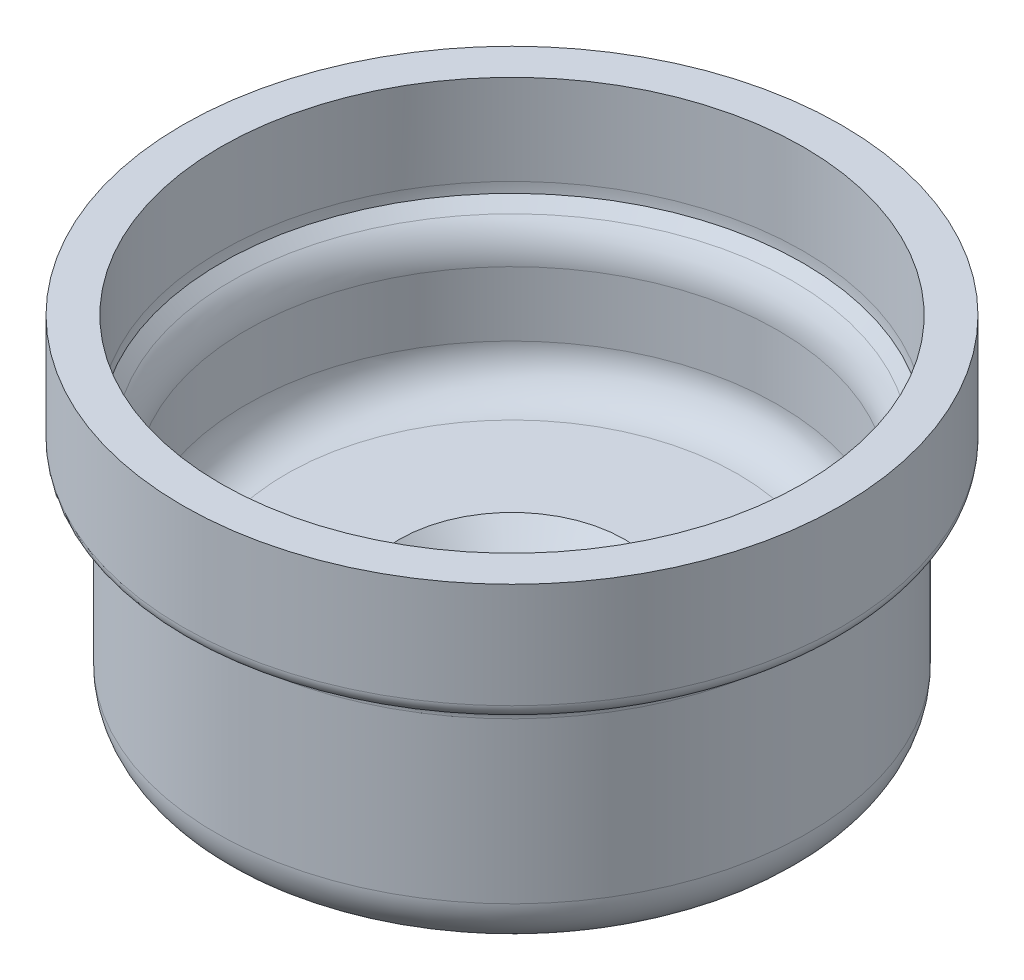
SolidWorks part; units mm, degrees
ref_plane "Front Plane" through (0, 0, 0) normal (0, 0, 1) x (1, 0, 0)
ref_plane "Top Plane" through (0, 0, 0) normal (0, 1, 0) x (1, 0, 0)
ref_plane "Right Plane" through (0, 0, 0) normal (1, 0, 0) x (0, 0, -1)
sketch "Sketch1" plane through (0, 0, 0) normal (0, 1, 0) x (1, 0, 0)
  circle A0 centre (0, 0) radius 26.55
  circle A1 centre (0, 0) radius 29.55
  dimension "D1" = 53.1
  dimension "D2" = 3
extrude "Boss-Extrude1" add sketch "Sketch1" along normal blind 15
sketch "Sketch2" plane through (0, 0, 0) normal (0, -1, 0) x (1, 0, 0)
  circle A0 centre (0, 0) radius 29.55 construction
  circle A1 centre (0, 0) radius 29.55
extrude "Boss-Extrude2" add sketch "Sketch2" along normal blind 10
chamfer "Chamfer1" distance 2.5 angle 45 1 edges at (0, 15, 26.55)
fillet "Fillet1" radius 4 1 edges at (0, 0, 26.55)
sketch "Sketch4" plane through (0, 15, 0) normal (0, 1, 0) x (1, 0, 0)
  circle A0 centre (0, 0) radius 32.9
  circle A1 centre (0, 0) radius 29.1
  dimension "D1" = 65.8
  dimension "D2" = 58.2
extrude "Boss-Extrude3" add sketch "Sketch4" along normal blind 10
sketch "Sketch5" plane through (0, 15, 0) normal (0, -1, 0) x (1, 0, 0)
  circle A0 centre (0, 0) radius 29.55 construction
  circle A1 centre (0, 0) radius 32.9
  circle A2 centre (0, 0) radius 32.9
  circle A3 centre (0, 0) radius 29.55
  dimension "D1" = 0
extrude "Boss-Extrude4" add sketch "Sketch5" along normal blind 2
fillet "Fillet3" radius 2 1 edges at (0, 13, -29.55)
fillet "Fillet6" radius 5 1 edges at (0, 12.5, 26.55)
fillet "Fillet7" radius 5 1 edges at (0, -10, -29.55)
fillet "Fillet8" radius 1.5 1 edges at (0, 13, -32.9)
sketch "Sketch6" plane through (0, 0, 0) normal (0, 1, 0) x (1, 0, 0)
  circle A0 centre (0, 0) radius 8.25
  dimension "D1" = 16.5
extrude "Cut-Extrude1" cut sketch "Sketch6" against normal blind 7
chamfer "Chamfer4" distance 3 angle 45 1 edges at (0, 0, 8.25)
sketch "Sketch7" plane through (0, -7, 0) normal (0, 1, 0) x (1, 0, 0)
  circle A0 centre (0, 0) radius 4.1
  dimension "D1" = 8.2
extrude "Cut-Extrude2" cut sketch "Sketch7" against normal through all
sketch "Sketch8" plane through (0, 0, 0) normal (0, 0, 1) x (1, 0, 0)
  line L0 (0, -10) -> (0, 27.7771) construction
  line L1 (-4.1, -10) -> (4.1, -10) construction
  line L2 (-24.55, -10) -> (24.55, -10) construction
  line L3 (22.55, -10) -> (12.55, -10)
  arc A0 (12.55, -10) -> (22.55, -10) centre (17.55, -10) cw
  dimension "D1" = 5
  dimension "D2" = 7
  dimension "D3" = 10
revolve "Cut-Revolve1" cut sketch "Sketch8" angle 360 about L0
fillet "Fillet9" radius 2 1 edges at (0, -10, -22.55)
fillet "Fillet10" radius 10 1 edges at (0, 15, 29.1)
